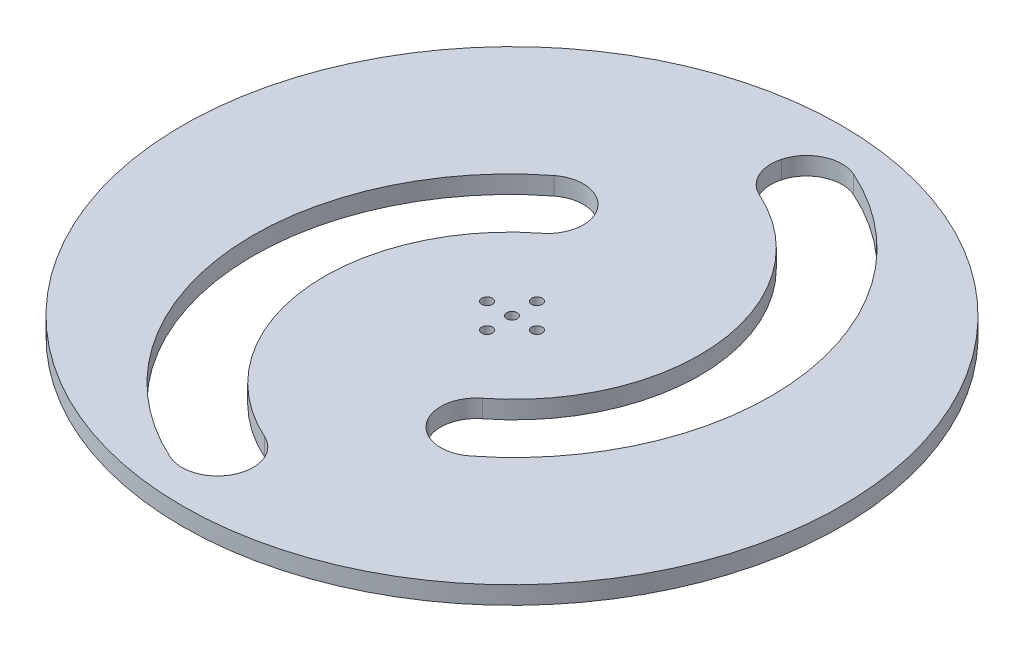
SolidWorks part; units mm, degrees
ref_plane "前视基准面" through (0, 0, 0) normal (0, 0, 1) x (1, 0, 0)
ref_plane "上视基准面" through (0, 0, 0) normal (0, 1, 0) x (1, 0, 0)
ref_plane "右视基准面" through (0, 0, 0) normal (1, 0, 0) x (0, 0, -1)
other "Configuration Table"
sketch "草图1" plane through (0, 0, 0) normal (0, 1, 0) x (1, 0, 0)
  circle A0 centre (0, 0) radius 92.5
  circle A1 centre (0, 0) radius 1.5
  circle A2 centre (0, 0) radius 7 construction
  circle A3 centre (0, 7) radius 1.5
  circle A4 centre (7, 0) radius 1.5
  circle A5 centre (0, -7) radius 1.5
  circle A6 centre (-7, 0) radius 1.5
  dimension "D1" = 3
  dimension "D2" = 185
  dimension "D3" = 14
  dimension "D4" = 3
  dimension "D5" = 3
  dimension "D6" = 3
  dimension "D7" = 3
extrude "凸台-拉伸1" add sketch "草图1" along normal blind 5
sketch "草图2" plane through (0, 5, 0) normal (0, 1, 0) x (1, 0, 0)
  line L0 (0, 0) -> (0, 150) construction
  line L1 (0, 0) -> (-60.6659, 166.6783) construction
  line L2 (2.5913, 86.2584) -> (-2.5913, 66.9416)
  line L3 (8.8813, -28.8148) -> (18.4803, -46.3606)
  line L6 (-8.8813, 28.8148) -> (-18.4803, 46.3606)
  line L7 (-2.5913, -86.2584) -> (2.5913, -66.9416)
  arc A0 (0, 76.6) -> (13.6808, -37.5877) centre (-16.0537, 16.7632) cw construction
  arc A1 (-2.5913, 66.9416) -> (8.8813, -28.8148) centre (-16.0537, 16.7632) cw
  arc A2 (2.5913, 86.2584) -> (18.4803, -46.3606) centre (-16.0537, 16.7632) cw
  arc A3 (-2.5913, 66.9416) -> (8.8813, -28.8148) centre (-16.0537, 16.7632) cw construction
  arc A5 (0, 76.6) -> (13.6808, -37.5877) centre (-16.0537, 16.7632) cw construction
  arc A8 (-2.5913, -86.2584) -> (-18.4803, 46.3606) centre (16.0537, -16.7632) cw
  arc A9 (2.5913, -66.9416) -> (-8.8813, 28.8148) centre (16.0537, -16.7632) cw
  arc A10 (0, -76.6) -> (-13.6808, 37.5877) centre (16.0537, -16.7632) cw construction
  point P27 (0, 0)
  point P30 (1.3102, 1.6636)
  dimension "D1" = 20
  dimension "D2" = 76.6
  dimension "D3" = 40
  dimension "D4" = 10
  dimension "D5" = 10
  dimension "D6" = 2
extrude "切除-拉伸1" cut sketch "草图2" against normal blind 30
fillet "圆角3" radius 10 8 edges at (-18.4803, 2.5, -46.3606) (-8.8813, 2.5, -28.8148) (-2.5913, 2.5, 86.2584) (2.5913, 2.5, 66.9416) (18.4803, 2.5, 46.3606) (8.8813, 2.5, 28.8148) (-2.5913, 2.5, -66.9416) (2.5913, 2.5, -86.2584)
extrude "凸台-拉伸2" add sketch "草图1<3>" along normal up to surface (5 mm away) contours A1 region at (0, 0, 0) up to face at (-21.468, 5, 21.2587)
sketch "草图1<3>" plane through (0, 0, 0) normal (0, 1, 0) x (1, 0, 0) same geometry as "草图1"
extrude "切除-拉伸2" cut sketch "草图1<5>" along normal up to surface (5 mm away) flip side to cut up to face at (-21.468, 5, 21.2587)
sketch "草图1<5>" plane through (0, 0, 0) normal (0, 1, 0) x (1, 0, 0) same geometry as "草图1"
